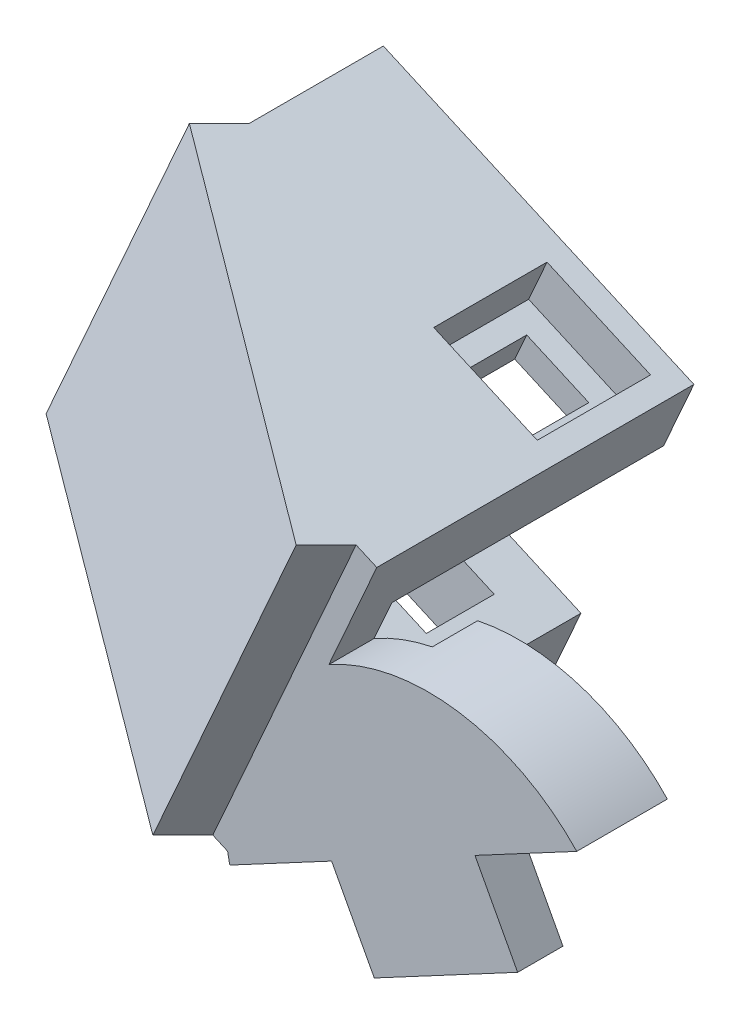
SolidWorks part; units mm, degrees
ref_plane "Front Plane" through (0, 0, 0) normal (0, 0, 1) x (1, 0, 0)
ref_plane "Top Plane" through (0, 0, 0) normal (0, 1, 0) x (1, 0, 0)
ref_plane "Right Plane" through (0, 0, 0) normal (1, 0, 0) x (0, 0, -1)
sketch "Sketch1" plane through (0, 0, 0) normal (0, 0, 1) x (1, 0, 0)
  line L0 (8.3098, 7.848) -> (-11.1433, -2.544)
  arc A0 (8.3098, 7.848) -> (-11.1433, -2.544) centre (0, 0) ccw
  dimension "D1" = 22.86
extrude "Boss-Extrude1" add sketch "Sketch1" along normal blind 5.08
sketch "Sketch2" plane through (0, 0, 0) normal (0, 0, -1) x (-1, 0, 0)
  line L1 (11.1433, -2.544) -> (-8.3098, 7.848) construction
  line L2 (-3.5143, 8.1659) -> (8.7414, 1.6188)
  line L3 (-3.5143, 8.1659) -> (8.7414, 1.6188)
  line L4 (-5.9625, 6.594) -> (8.7959, -1.29)
  arc A1 (-3.5143, 8.1659) -> (8.7414, 1.6188) centre (0, 0) cw
  arc A2 (8.7414, 1.6188) -> (-3.5143, 8.1659) centre (0, 0) ccw
  arc A3 (8.7414, 1.6188) -> (-3.5143, 8.1659) centre (0, 0) ccw
  arc A4 (-5.9625, 6.594) -> (8.7959, -1.29) centre (0, 0) cw
  line M4 (-8.3098, 7.848) -> (11.1433, -2.544)
  dimension "D2" = 0
  dimension "D1" = 2.54
extrude "Cut-Extrude1" cut sketch "Sketch2" against normal blind 2.54 contours A1 L3 | A4 L3 M4 region at (-3.2551, 6.0933, 0) region at (-1.997, 3.7382, 0)
sketch "Sketch3" plane through (-1.4167, 2.652, 0) normal (0.4712, -0.882, 0) x (0.882, 0.4712, 0)
  line L0 (-11.0275, 5.08) -> (11.0275, 5.08) construction
  line L1 (4.5561, 5.08) -> (-4.5561, 5.08)
  line L2 (4.5561, 5.08) -> (4.5561, 2.54)
  line L3 (4.5561, 2.54) -> (-4.5561, 2.54)
  line L4 (-4.5561, 5.08) -> (-4.5561, 2.54)
  line L5 (8.3661, 2.54) -> (-8.3661, 2.54) construction
  line L6 (8.3661, 2.54) -> (8.3661, 0) construction
  line L7 (-8.3661, 2.54) -> (-8.3661, 0) construction
  dimension "D1" = 3.81
  dimension "D2" = 3.81
extrude "Boss-Extrude2" add sketch "Sketch3" along normal blind 5.08
sketch "Sketch4" plane through (0, 0, 5.08) normal (0, 0, 1) x (1, 0, 0)
  line L0 (-2.9016, 16.0296) -> (-20.3151, 23.7544)
  line L1 (-20.3151, 23.7544) -> (-28.349, 5.6444)
  line L2 (-28.349, 5.6444) -> (-10.9355, -2.0805)
  line L3 (-10.9355, -2.0805) -> (-2.9016, 16.0296)
  point P2 (0, 0)
  dimension "D1" = 19.05
  dimension "D2" = 19.812
  dimension "D3" = 0.508
extrude "Boss-Extrude3" add sketch "Sketch4" against normal blind 17.78 contours L3 L0 L1 L2
sketch "Sketch5" plane through (0, 0, -12.7) normal (0, 0, -1) x (-1, 0, 0)
  line L4 (8.4321, 13.8981) -> (0.6086, 10.4275)
  line L5 (0.6086, 10.4275) -> (5.2435, -0.0206)
  line L6 (5.2435, -0.0206) -> (13.067, 3.45)
  line L8 (13.067, 3.45) -> (22.8185, 7.7759)
  line L9 (22.8185, 7.7759) -> (18.1836, 18.224)
  line L10 (18.1836, 18.224) -> (8.4321, 13.8981)
  line L11 (8.4321, 13.8981) -> (13.067, 3.45)
  line L12 (13.067, 3.45) -> (22.8185, 7.7759)
  line L13 (22.8185, 7.7759) -> (18.1836, 18.224)
  line L14 (18.1836, 18.224) -> (8.4321, 13.8981)
  dimension "D1" = 4.191
extrude "Cut-Extrude2" cut sketch "Sketch5" against normal blind 15.24
sketch "Sketch6" plane through (-0.8699, -1.9608, 0) normal (0.4055, 0.9141, 0) x (0.9141, -0.4055, 0)
  line L0 (-24.0114, -2.54) -> (-38.3558, 12.7)
  line L1 (-38.3558, 12.7) -> (-24.0114, 12.7)
  line L2 (-24.0114, 12.7) -> (-24.0114, -2.54)
  point P3 (-43.1108, 12.7)
  point P6 (-34.2041, 12.7)
  point P7 (-38.3558, 12.7)
extrude "Cut-Extrude3" cut sketch "Sketch6" along normal up to surface (11.43 mm away) up to face at (-11.3924, 15.2113, -5.08)
chamfer "Chamfer1" distance 17.78 angle 30 1 edges at (-24.332, 14.6994, 5.08) first distance on face at (-6.5248, 5.7095, 5.08)
sketch "Sketch7" plane through (5.4645, 12.3182, 0) normal (0.4055, 0.9141, 0) x (0.9141, -0.4055, 0)
  line L0 (-9.1524, 12.7) -> (-9.1524, -5.08) construction
  line L1 (-11.6924, 10.16) -> (-15.5024, 10.16)
  line L2 (-11.6924, 10.16) -> (-11.6924, 6.35)
  line L3 (-11.6924, 6.35) -> (-15.5024, 6.35)
  line L4 (-15.5024, 10.16) -> (-15.5024, 6.35)
  line L5 (-9.1524, 12.7) -> (-28.2024, 12.7) construction
  dimension "D1" = 2.54
  dimension "D2" = 2.54
  dimension "D3" = 3.81
  dimension "D4" = 3.81
extrude "Cut-Extrude4" cut sketch "Sketch7" against normal blind 25.4
sketch "Sketch8" plane through (5.4645, 12.3182, 0) normal (0.4055, 0.9141, 0) x (0.9141, -0.4055, 0)
  line L8 (-10.4224, 11.43) -> (-16.7724, 11.43)
  line L9 (-10.4224, 5.08) -> (-10.4224, 11.43)
  line L10 (-16.7724, 5.08) -> (-10.4224, 5.08)
  line L11 (-16.7724, 11.43) -> (-16.7724, 5.08)
  line L12 (-10.4224, 11.43) -> (-16.7724, 11.43)
  line L13 (-10.4224, 5.08) -> (-10.4224, 11.43)
  line L14 (-16.7724, 5.08) -> (-10.4224, 5.08)
  line L15 (-16.7724, 11.43) -> (-16.7724, 5.08)
  dimension "D1" = 1.27
extrude "Cut-Extrude5" cut sketch "Sketch8" against normal blind 2.54
sketch "Sketch10" plane through (-4.3925, 1.9486, 8.323) normal (-0.457, 0.2028, 0.866) x (0.8894, 0.1042, 0.445)
  line L0 (-26.9342, 6.6778) -> (-17.9018, 24.311)
  line L1 (-17.9018, 24.311) -> (0.371, 14.951)
  line L2 (0.371, 14.951) -> (-8.6615, -2.6823)
  line L3 (-8.6615, -2.6823) -> (-26.9342, 6.6778)
extrude "Boss-Extrude4" add sketch "Sketch10" along normal blind 2.54 and the other way blind 2.54
